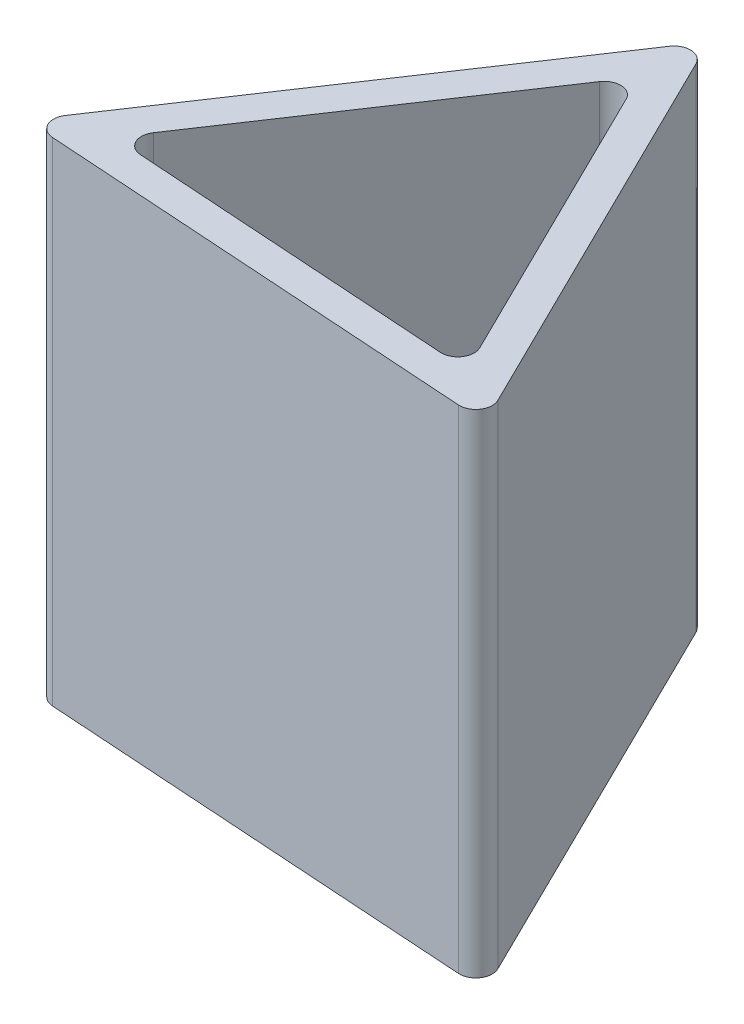
SolidWorks part; units mm, degrees
ref_plane "Front Plane" through (0, 0, 0) normal (0, 0, 1) x (1, 0, 0)
ref_plane "Top Plane" through (0, 0, 0) normal (0, 1, 0) x (1, 0, 0)
ref_plane "Right Plane" through (0, 0, 0) normal (1, 0, 0) x (0, 0, -1)
sketch "Sketch1" plane through (0, 0, 0) normal (0, 1, 0) x (1, 0, 0)
  line L0 (-0.2633, 13.2916) -> (-13.0895, -5.8864)
  line L1 (0, 17.2829) -> (-16.6778, -7.654)
  line L2 (-16.6778, -7.654) -> (13.2572, -9.6289)
  line L3 (13.2572, -9.6289) -> (0, 17.2829)
  line L4 (-13.0895, -5.8864) -> (9.9322, -7.4052)
  line L5 (9.9322, -7.4052) -> (-0.2633, 13.2916)
  circle A0 centre (-1.1402, 0) radius 8.6603 construction
  dimension "D1" = 30
  dimension "D2" = 2
extrude "Boss-Extrude1" add sketch "Sketch1" along normal blind 30
fillet "Fillet1" radius 1 6 edges at (9.9322, 15, 7.4052) (-0.2633, 15, -13.2916) (-13.0895, 15, 5.8864) (-16.6778, 15, 7.654) (13.2572, 15, 9.6289) (0, 15, -17.2829)
